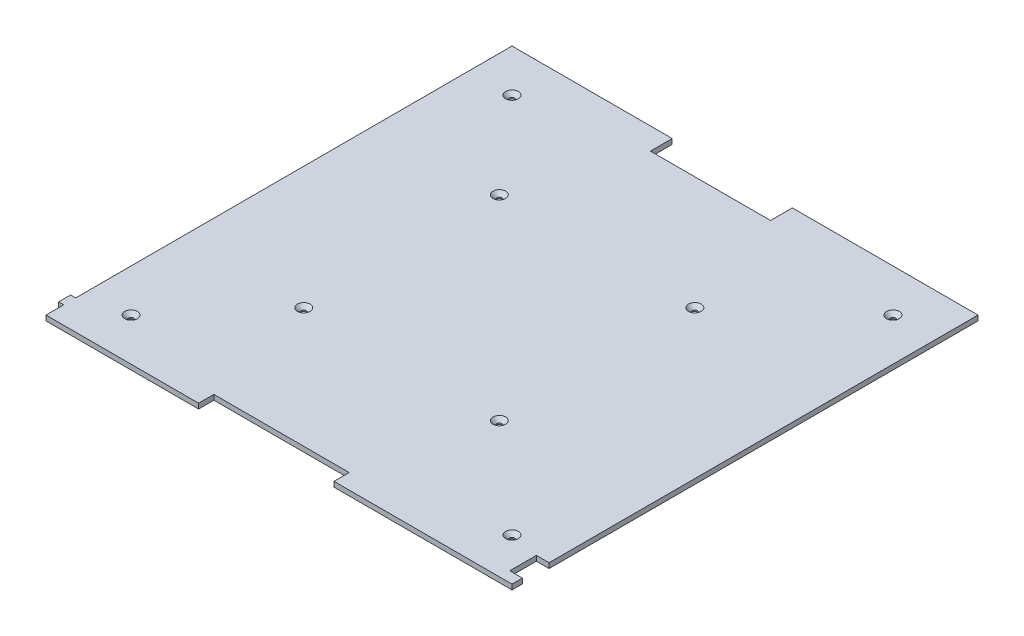
SolidWorks part; units mm, degrees
ref_plane "Front Plane" through (0, 0, 0) normal (0, 0, 1) x (1, 0, 0)
ref_plane "Top Plane" through (0, 0, 0) normal (0, 1, 0) x (1, 0, 0)
ref_plane "Right Plane" through (0, 0, 0) normal (1, 0, 0) x (0, 0, -1)
sketch "Sketch1" plane through (0, 0, 0) normal (0, 1, 0) x (1, 0, 0)
  line L0 (-92, 92) -> (-92, -79.8) construction
  line L1 (-28.4, 92) -> (-92, 92) construction
  line L2 (-28.4, 83.4) -> (-28.4, 92) construction
  line L3 (18.4, 83.4) -> (-28.4, 83.4) construction
  line L4 (18.4, 92) -> (18.4, 83.4) construction
  line L5 (92, 92) -> (18.4, 92) construction
  line L6 (92, -77.4) -> (92, 92) construction
  line L7 (87, -77.4) -> (92, -77.4) construction
  line L8 (87, -87.4) -> (87, -77.4) construction
  line L9 (92, -87.4) -> (87, -87.4) construction
  line L10 (92, -92) -> (92, -87.4) construction
  line L11 (21.4, -92) -> (92, -92) construction
  line L12 (21.4, -86) -> (21.4, -92) construction
  line L13 (-31.4, -86) -> (21.4, -86) construction
  line L14 (-31.4, -92) -> (-31.4, -86) construction
  line L15 (-92, -92) -> (-31.4, -92) construction
  line L16 (-92, -85) -> (-92, -92) construction
  line L17 (-94, -85) -> (-92, -85) construction
  line L18 (-94, -79.8) -> (-94, -85) construction
  line L19 (-92, -79.8) -> (-94, -79.8) construction
  line L20 (-91.75, 91.75) -> (-91.75, -80.05)
  line L21 (-91.75, -80.05) -> (-93.75, -80.05)
  line L22 (-93.75, -80.05) -> (-93.75, -84.75)
  line L23 (-93.75, -84.75) -> (-91.75, -84.75)
  line L24 (-91.75, -84.75) -> (-91.75, -91.75)
  line L25 (-91.75, -91.75) -> (-31.65, -91.75)
  line L26 (-31.65, -91.75) -> (-31.65, -85.75)
  line L27 (-31.65, -85.75) -> (21.65, -85.75)
  line L28 (21.65, -85.75) -> (21.65, -91.75)
  line L29 (21.65, -91.75) -> (91.75, -91.75)
  line L30 (91.75, -91.75) -> (91.75, -87.65)
  line L31 (91.75, -87.65) -> (86.75, -87.65)
  line L32 (86.75, -87.65) -> (86.75, -77.15)
  line L33 (86.75, -77.15) -> (91.75, -77.15)
  line L34 (91.75, -77.15) -> (91.75, 91.75)
  line L35 (91.75, 91.75) -> (18.65, 91.75)
  line L36 (18.65, 91.75) -> (18.65, 83.15)
  line L37 (18.65, 83.15) -> (-28.65, 83.15)
  line L38 (-28.65, 83.15) -> (-28.65, 91.75)
  line L39 (-28.65, 91.75) -> (-91.75, 91.75)
  dimension "D1" = 184
  dimension "D2" = 184
  dimension "D3" = 8.6
  dimension "D4" = 63.6
  dimension "D5" = 46.8
  dimension "D6" = 2
  dimension "D7" = 7
  dimension "D8" = 5.2
  dimension "D9" = 4.6
  dimension "D10" = 10
  dimension "D11" = 70.6
  dimension "D12" = 52.8
  dimension "D13" = 5
  dimension "D14" = 6
  dimension "D15" = 92
  dimension "D16" = 92
  dimension "D17" = 0.25
extrude "Boss-Extrude1" add sketch "Sketch1" along normal blind 2
sketch "Sketch2" plane through (0, 0, 0) normal (0, -1, 0) x (1, 0, 0)
  circle A0 centre (75, -75) radius 1
  circle A1 centre (-75, -75) radius 1
  circle A2 centre (-75, 75) radius 1
  circle A3 centre (75, 75) radius 1
  circle A4 centre (33.5, -38.5) radius 1
  circle A5 centre (33.5, 38.5) radius 1
  circle A6 centre (-43.5, -38.5) radius 1
  circle A7 centre (-43.5, 38.5) radius 1
  dimension "D1" = 2
  dimension "D2" = 2
  dimension "D3" = 2
  dimension "D4" = 2
  dimension "D5" = 2
  dimension "D6" = 2
  dimension "D7" = 2
  dimension "D8" = 2
extrude "Cut-Extrude1" cut sketch "Sketch2" against normal through all
chamfer "Chamfer1" distance 1.5 angle 45 8 edges at (75, 2, -76) (33.5, 2, -39.5) (75, 2, 74) (33.5, 2, 37.5) (-43.5, 2, 37.5) (-43.5, 2, -39.5) (-75, 2, -76) (-75, 2, 74)
